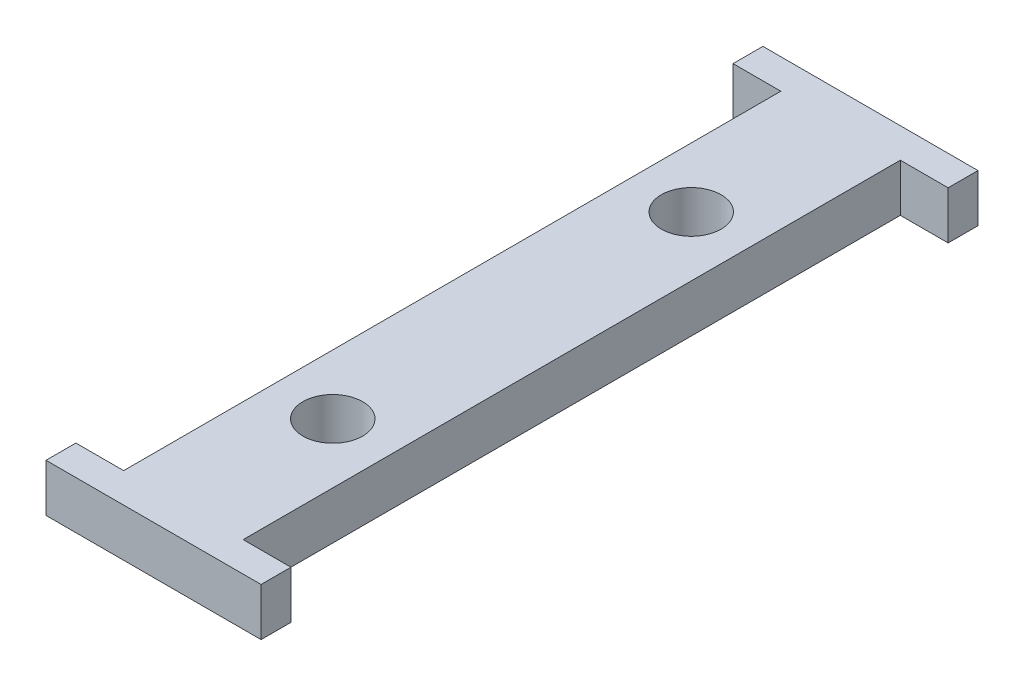
SolidWorks part; units mm, degrees
material "Pine"
ref_plane "Front Plane" through (0, 0, 0) normal (0, 0, 1) x (1, 0, 0)
ref_plane "Top Plane" through (0, 0, 0) normal (0, 1, 0) x (1, 0, 0)
ref_plane "Right Plane" through (0, 0, 0) normal (1, 0, 0) x (0, 0, -1)
sketch "Sketch1" plane through (0, 0, 0) normal (0, 1, 0) x (1, 0, 0)
  line L4 (-11.43, 0) -> (11.43, 0)
  line L5 (-11.43, 0) -> (-11.43, 3.175)
  line L6 (-11.43, 3.175) -> (-6.35, 3.175)
  line L7 (-6.35, 3.175) -> (-6.35, 73.025)
  line L8 (-6.35, 73.025) -> (-11.43, 73.025)
  line L9 (-11.43, 73.025) -> (-11.43, 76.2)
  line L10 (-11.43, 76.2) -> (11.43, 76.2)
  line L11 (11.43, 76.2) -> (11.43, 73.025)
  line L12 (11.43, 73.025) -> (6.35, 73.025)
  line L13 (6.35, 73.025) -> (6.35, 3.175)
  line L14 (6.35, 3.175) -> (11.43, 3.175)
  line L15 (11.43, 3.175) -> (11.43, 0)
  point P4 (0, 0)
  dimension "D1" = 3.175
  dimension "D2" = 76.2
  dimension "D3" = 12.7
  dimension "D4" = 5.08
extrude "Boss-Extrude1" add sketch "Sketch1" along normal blind 5.08
hole_wizard "1/4-20 Tapped Hole1" positions "Sketch2" profile "Sketch3" tap size "1/4-20" standard "ANSI Inch"
sketch "Sketch2" plane through (0, 5.08, 0) normal (0, 1, 0) x (1, 0, 0)
  line L2 (-6.35, 38.1) -> (6.35, 38.1) construction
  line L3 (-6.35, 73.025) -> (-6.35, 3.175) construction
  line L4 (6.35, 3.175) -> (6.35, 73.025) construction
  point P0 (0, 57.15)
  point P18 (0, 0)
  point P19 (0, 19.05)
  point P20 (0, 0)
  dimension "D1" = 38.1
sketch "Sketch3" plane through (0, 5.08, -57.15) normal (1, 0, 0) x (0, 0, 1)
  line L0 (0, 0) -> (0, 18.4177)
  line L1 (0, 18.4177) -> (3.175, 16.51)
  line L2 (3.175, 16.51) -> (3.175, 0)
  line L5 (3.175, 0) -> (0, 0)
  line L10 (0, 18.4177) -> (-3.175, 16.51) construction
  line L11 (0, -6.35) -> (0, 107.95) construction
  dimension "Tap Drill Dia." = 6.35
  dimension "Tap Drill Depth" = 16.51
  dimension "Drill Angle" = 118
cosmetic thread "Hole Thread1"
cosmetic thread "Hole Thread2"
